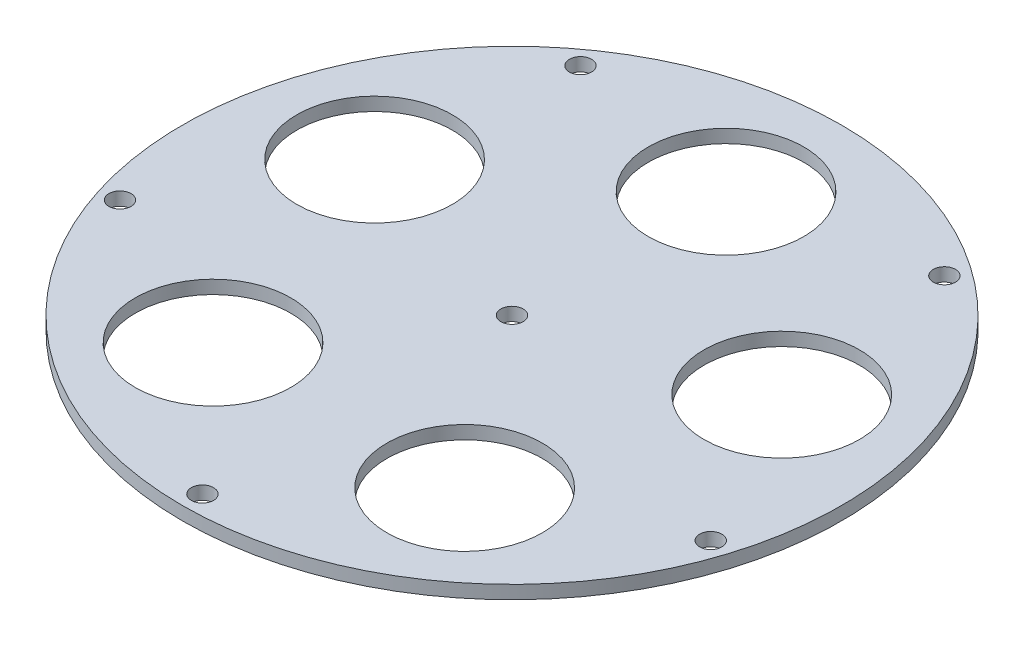
SolidWorks part; units mm, degrees
ref_plane "Front Plane" through (0, 0, 0) normal (0, 0, 1) x (1, 0, 0)
ref_plane "Top Plane" through (0, 0, 0) normal (0, 1, 0) x (1, 0, 0)
ref_plane "Right Plane" through (0, 0, 0) normal (1, 0, 0) x (0, 0, -1)
sketch "Sketch1" plane through (0, 0, 0) normal (0, 1, 0) x (1, 0, 0)
  line L0 (0, 0) -> (0, 74.1827) construction
  line L1 (70.5519, 22.9237) -> (0, 0) construction
  line L2 (0, 0) -> (43.6035, -60.015) construction
  line L3 (-43.6035, -60.015) -> (0, 0) construction
  line L4 (0, 0) -> (-70.5519, 22.9237) construction
  line L5 (-45.8244, 14.8893) -> (-28.3211, -38.9806) construction
  line L6 (-43.6035, 60.015) -> (0, 0) construction
  line L7 (0, 0) -> (43.6035, 60.015) construction
  line L8 (70.5519, -22.9237) -> (0, 0) construction
  line L9 (0, 0) -> (0, -74.1827) construction
  line L10 (-70.5519, -22.9237) -> (0, 0) construction
  line L11 (-74.1827, 0) -> (74.1827, 0) construction
  circle A0 centre (0, 0) radius 74.1827
  circle A1 centre (0, 48.1827) radius 17.5
  circle A2 centre (45.8244, 14.8893) radius 17.5
  circle A3 centre (28.3211, -38.9806) radius 17.5
  circle A4 centre (-28.3211, -38.9806) radius 17.5
  circle A5 centre (-45.8244, 14.8893) radius 17.5
  circle A7 centre (40.9584, 56.3745) radius 2.5
  circle A8 centre (66.2722, -21.5331) radius 2.5
  circle A9 centre (0, -69.6827) radius 2.5
  circle A10 centre (-66.605, -21.6413) radius 2.5
  circle A11 centre (-40.9584, 56.3745) radius 2.5
  circle A24 centre (0, 0) radius 2.5
  dimension "D1" = 72
  dimension "D5" = 35
  dimension "D6" = 35
  dimension "D7" = 35
  dimension "D8" = 35
  dimension "D9" = 35
  dimension "D16" = 90
  dimension "D21" = 5
  dimension "D22" = 5
  dimension "D23" = 5
  dimension "D24" = 5
  dimension "D25" = 5
  dimension "D31" = 5
  dimension "D2" = 72
  dimension "D3" = 72
  dimension "D4" = 72
  dimension "D10" = 26
  dimension "D11" = 26
  dimension "D12" = 26
  dimension "D13" = 26
  dimension "D14" = 26
  dimension "D15" = 48.1827
  dimension "D17" = 36
  dimension "D18" = 36
  dimension "D19" = 36
  dimension "D20" = 36
  dimension "D26" = 4.5
  dimension "D27" = 4.5
  dimension "D28" = 4.5
  dimension "D29" = 4.5
  dimension "D30" = 4.15
extrude "Boss-Extrude2" add sketch "Sketch1" against normal blind 3 contours A0
extrude "Cut-Extrude1" cut sketch "Sketch1<4>" against normal blind 4 contours A4 | A3 | A2 | A1 | A5
sketch "Sketch1<4>" plane through (0, 0, 0) normal (0, 1, 0) x (1, 0, 0) same geometry as "Sketch1"
extrude "Cut-Extrude2" cut sketch "Sketch1<5>" against normal blind 4 contours A10 | A9 | A8 | A7 | A11
sketch "Sketch1<5>" plane through (0, 0, 0) normal (0, 1, 0) x (1, 0, 0) same geometry as "Sketch1"
extrude "Cut-Extrude5" cut sketch "Sketch1<10>" against normal blind 10 contours A24
sketch "Sketch1<10>" plane through (0, 0, 0) normal (0, 1, 0) x (1, 0, 0) same geometry as "Sketch1"
sketch "Sketch2" plane through (0, 0, 0) normal (0, 1, 0) x (1, 0, 0)
  line L0 (-42.4789, -28.6944) -> (-14.1633, -49.2668) construction
  line L1 (-43.6035, -60.015) -> (0, 0) construction
  line L2 (-42.4789, -28.6944) -> (-14.1633, -49.2668)
  line L3 (-42.4789, -28.6944) -> (-53.0588, -43.2564)
  line L4 (-14.1633, -49.2668) -> (-24.7432, -63.8289)
  line L5 (-53.0588, -43.2564) -> (-24.7432, -63.8289)
  circle A0 centre (-28.3211, -38.9806) radius 17.5 construction
